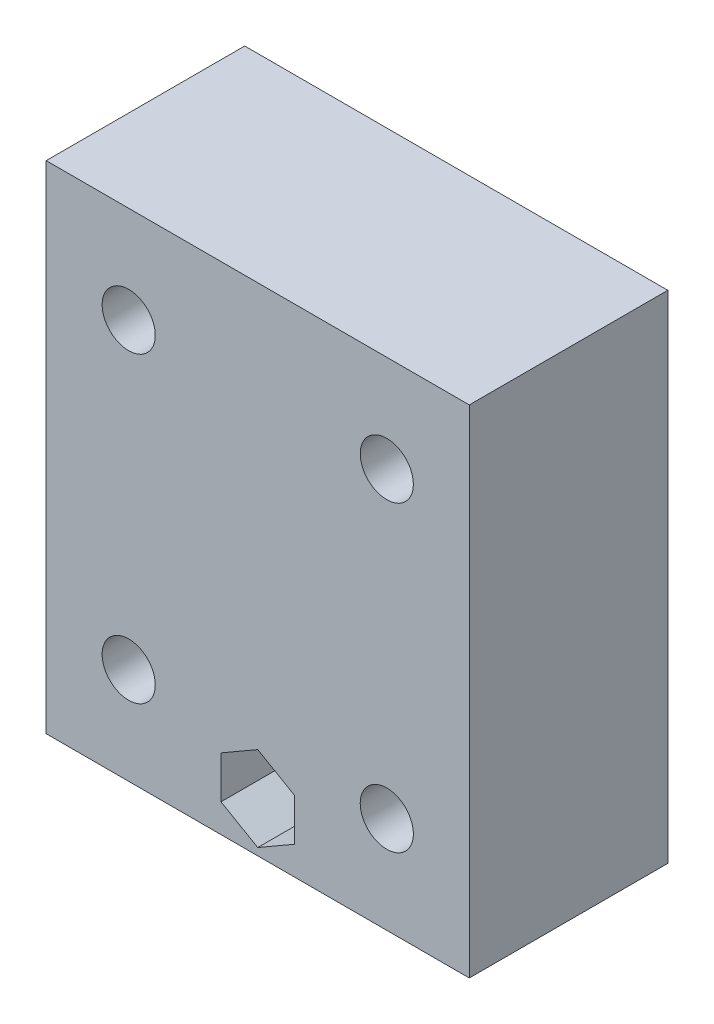
SolidWorks part; units mm, degrees
ref_plane "Front Plane" through (0, 0, 0) normal (0, 0, 1) x (1, 0, 0)
ref_plane "Top Plane" through (0, 0, 0) normal (0, 1, 0) x (1, 0, 0)
ref_plane "Right Plane" through (0, 0, 0) normal (1, 0, 0) x (0, 0, -1)
sketch "Sketch1" plane through (0, 0, 0) normal (0, 0, 1) x (1, 0, 0)
  line L0 (0, 25) -> (0, -25) construction
  line L1 (21.3115, 25) -> (-21.3115, 25)
  line L2 (21.3115, 25) -> (21.3115, -25)
  line L3 (21.3115, -25) -> (-21.3115, -25)
  line L4 (-21.3115, 25) -> (-21.3115, -25)
  line L5 (21.3115, 25) -> (-21.3115, -25) construction
  line L6 (21.3115, -25) -> (-21.3115, 25) construction
  line L7 (-21.3115, 0) -> (21.3115, 0) construction
  circle A0 centre (-13, -15.25) radius 2.677
  circle A1 centre (13, -15.25) radius 2.677
  circle A2 centre (13, 15.25) radius 2.677
  circle A3 centre (-13, 15.25) radius 2.677
  point P0 (0, 0)
  dimension "D1" = 30.5
  dimension "D2" = 26
  dimension "D3" = 50
extrude "Boss-Extrude1" add sketch "Sketch1" along normal blind 20
sketch "Sketch2" plane through (0, 0, 0) normal (0, 0, 1) x (1, 0, 0)
  circle A0 centre (0, 0) radius 8.73
  dimension "D1" = 17.46
extrude "Cut-Extrude2" cut sketch "Sketch2" along normal blind 7.94
sketch "Sketch3" plane through (0, 0, 0) normal (0, 0, -1) x (-1, 0, 0)
  circle A0 centre (0, -20) radius 2.2
  dimension "D1" = 4.4
  dimension "D2" = 20
extrude "Cut-Extrude3" cut sketch "Sketch3" against normal blind 10
sketch "Sketch5" plane through (0, 0, 0) normal (0, 0, -1) x (-1, 0, 0)
  line L1 (0, -15.7276) -> (-3.7, -17.8638)
  line L2 (-3.7, -17.8638) -> (-3.7, -22.1362)
  line L3 (-3.7, -22.1362) -> (0, -24.2724)
  line L4 (0, -24.2724) -> (3.7, -22.1362)
  line L5 (3.7, -22.1362) -> (3.7, -17.8638)
  line L6 (3.7, -17.8638) -> (0, -15.7276)
  circle A0 centre (0, -20) radius 3.7 construction
  dimension "D1" = 3.7
extrude "Cut-Extrude4" cut sketch "Sketch5" against normal through all from offset 7 offset against normal yes
